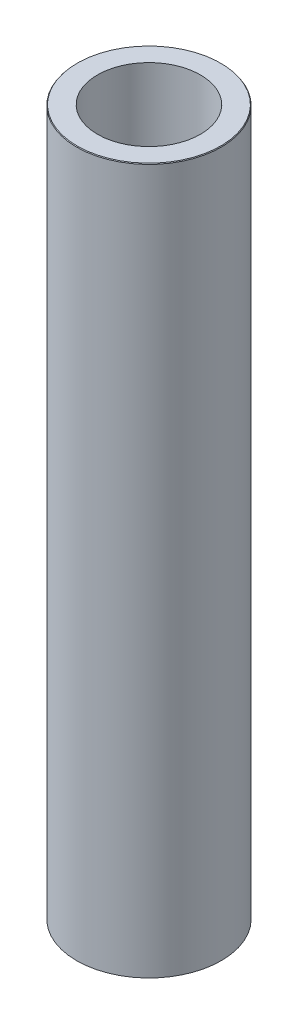
SolidWorks part; units mm, degrees
ref_plane "Front Plane" through (0, 0, 0) normal (0, 0, 1) x (1, 0, 0)
ref_plane "Top Plane" through (0, 0, 0) normal (0, 1, 0) x (1, 0, 0)
ref_plane "Right Plane" through (0, 0, 0) normal (1, 0, 0) x (0, 0, -1)
sketch "Sketch1" plane through (0, 0, 0) normal (0, 1, 0) x (1, 0, 0)
  circle A0 centre (0, 0) radius 40
  dimension "SHAFT_OD" = 80
extrude "Boss-Extrude1" add sketch "Sketch1" along normal blind 390.5207
sketch "Sketch2" plane through (0, 0, 0) normal (0, 1, 0) x (1, 0, 0)
  circle A0 centre (0, 0) radius 28.4848
  dimension "BORE_D" = 56.9697
extrude "Cut-Extrude1" cut sketch "Sketch2" along normal through all
chamfer "Chamfer1" distance 0.4079 angle 36.141 2 edges at (0, 390.5207, 40) (0, 0, 40) first distance on face at (0, 390.5207, 40) first distance on face at (0, 0, 28.4848)
